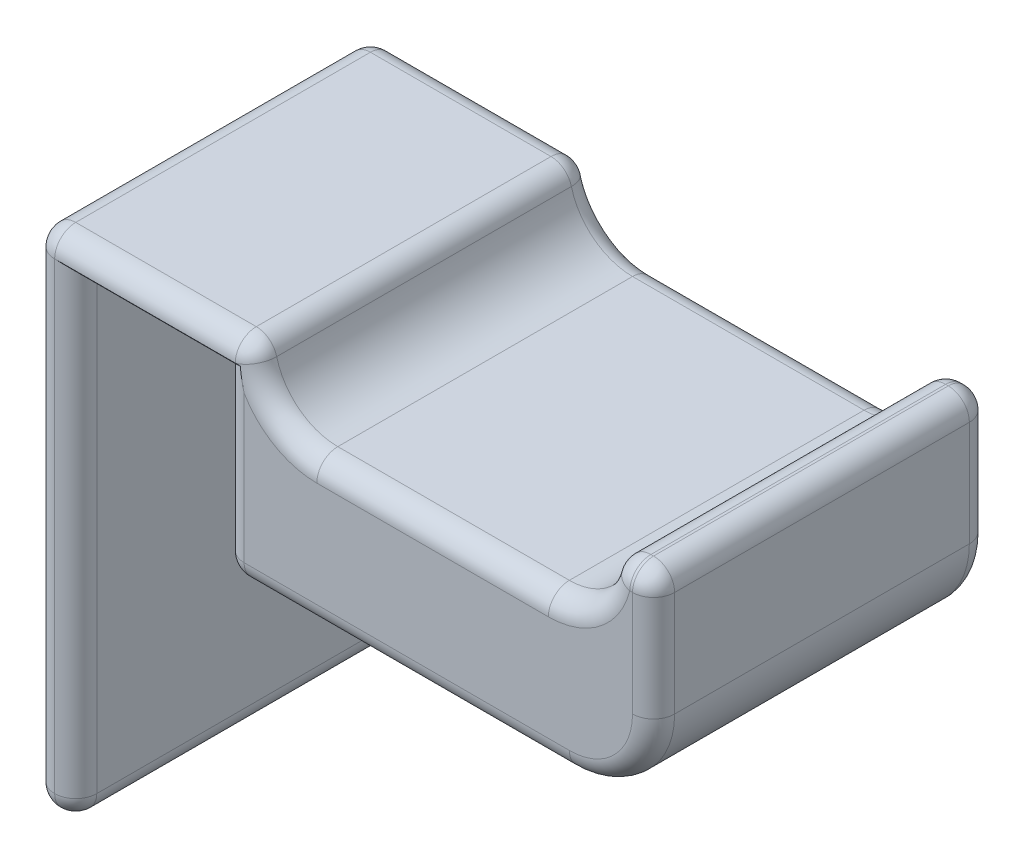
SolidWorks part; units mm, degrees
ref_plane "Front Plane" through (0, 0, 0) normal (0, 0, 1) x (1, 0, 0)
ref_plane "Top Plane" through (0, 0, 0) normal (0, 1, 0) x (1, 0, 0)
ref_plane "Right Plane" through (0, 0, 0) normal (1, 0, 0) x (0, 0, -1)
sketch "Sketch1" plane through (0, 0, 0) normal (0, 0, 1) x (1, 0, 0)
  line L0 (2.5, 0) -> (21.128, 0)
  line L1 (21.128, 0) -> (23.9455, 0)
  line L2 (33.628, -7.5) -> (61.128, -7.5)
  line L3 (70.8104, 0) -> (71.128, 0)
  line L4 (73.628, -2.5) -> (73.628, -15)
  line L5 (63.628, -25) -> (25, -25)
  line L6 (22.5, -22.5) -> (22.5, -3.5)
  line L7 (22.5, -3.5) -> (5, -3.5)
  line L8 (5, -3.5) -> (5, -60)
  line L9 (5, -60) -> (2.5, -60)
  line L10 (0, -57.5) -> (0, -2.5)
  line L11 (25.4764, -0.5236) -> (22.5, -3.5) construction
  arc A0 (26.3661, -1.875) -> (33.628, -7.5) centre (33.628, 0) ccw
  arc A1 (61.128, -7.5) -> (68.3898, -1.875) centre (61.128, 0) ccw
  arc A2 (73.628, -15) -> (63.628, -25) centre (63.628, -15) cw
  arc A3 (71.128, 0) -> (73.628, -2.5) centre (71.128, -2.5) cw
  arc A4 (2.5, -60) -> (0, -57.5) centre (2.5, -57.5) cw
  arc A5 (2.5, 0) -> (0, -2.5) centre (2.5, -2.5) ccw
  arc A6 (68.3898, -1.875) -> (70.8104, 0) centre (70.8104, -2.5) cw
  arc A7 (23.9455, 0) -> (26.3661, -1.875) centre (23.9455, -2.5) cw
  arc A8 (25, -25) -> (22.5, -22.5) centre (25, -22.5) cw
  point P18 (73.628, -25)
  point P21 (73.628, 0)
  point P24 (0, -60)
  point P27 (0, 0)
  point P30 (68.628, 0)
  point P33 (26.128, 0)
  dimension "D11" = 10
  dimension "D12" = 2.5
  dimension "D13" = 2.5
  dimension "D1" = 5
  dimension "D2" = 17.5
  dimension "D3" = 3.5
  dimension "D4" = 60
  dimension "D5" = 25
  dimension "D6" = 7.5
  dimension "D7" = 135
  dimension "D8" = 42.5
  dimension "D9" = 5
  dimension "D10" = 5
extrude "Boss-Extrude1" add sketch "Sketch1" along normal blind 40 contours L7 L8 L9 A4 L10 A5 L0 L1 A7 A0 L2 A1 A6 L3 A3 L4 A2 L5 A8 L6
fillet "Fillet1" radius 2.5 34 edges at (3.75, -60, 0) (0.7322, -59.2678, 0) (0, -30, 0) (0.7322, -0.7322, 0) (44.314, -25, 0) (70.699, -22.0711, 0) (73.628, -8.75, 0) (72.8957, -0.7322, 0) (70.9692, 0, 0) (69.2795, -0.5236, 0) (65.7207, -5.9293, 0) (47.378, -7.5, 0) (29.0352, -5.9293, 0) (25.4764, -0.5236, 0) (3.75, -60, 40) (0.7322, -59.2678, 40) (0, -30, 40) (0.7322, -0.7322, 40) (44.314, -25, 40) (70.699, -22.0711, 40) (73.628, -8.75, 40) (72.8957, -0.7322, 40) (70.9692, 0, 40) (69.2795, -0.5236, 40) (65.7207, -5.9293, 40) (47.378, -7.5, 40) (29.0352, -5.9293, 40) (25.4764, -0.5236, 40) (13.2227, 0, 0) (13.2227, 0, 40) (22.5, -13, 0) (23.2322, -24.2678, 0) (22.5, -13, 40) (23.2322, -24.2678, 40)
fillet "Fillet2" radius 2.5 6 edges at (5, -30.5, 0) (5, -59.2678, 0.7322) (5, -60, 20) (5, -59.2678, 39.2678) (14.6302, -3.5, 40) (5, -30.5, 40)
fillet "Fillet3" radius 2.5 1 edges at (13.3802, -3.5, 0)
